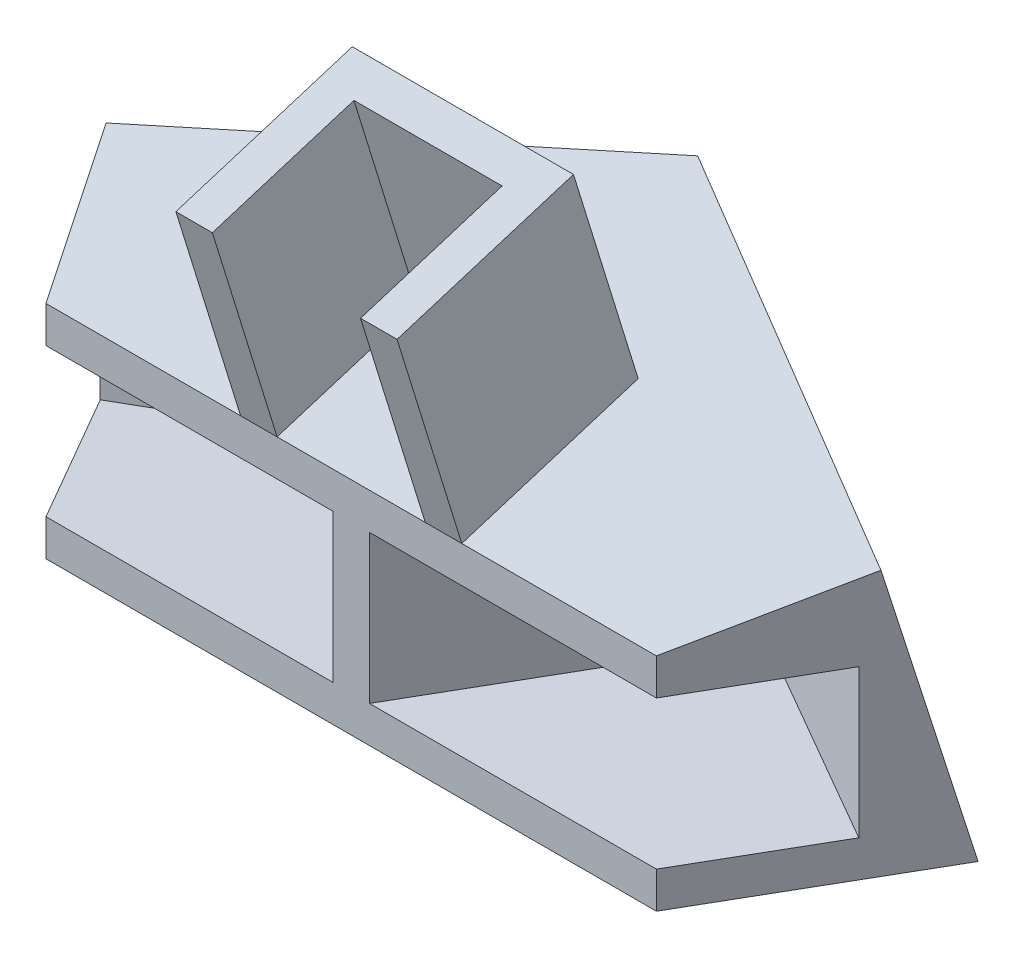
SolidWorks part; units mm, degrees
ref_plane "Front Plane" through (0, 0, 0) normal (0, 0, 1) x (1, 0, 0)
ref_plane "Top Plane" through (0, 0, 0) normal (0, 1, 0) x (1, 0, 0)
ref_plane "Right Plane" through (0, 0, 0) normal (1, 0, 0) x (0, 0, -1)
sketch "Sketch1" plane through (0, 0, 0) normal (0, 1, 0) x (1, 0, 0)
  line L0 (0, 0) -> (0, -24.1399) construction
  line L4 (0, 0) -> (-41.8115, -24.1399) construction
  line L5 (-41.8115, -24.1399) -> (0, -24.1399) construction
  line L6 (-41.8115, -24.1399) -> (-44.3115, -19.8098) construction
  line L7 (-44.3115, -19.8098) -> (0, 5.7735) construction
  line L8 (0, 5.7735) -> (0, 0) construction
  line L9 (-44.3115, -19.8098) -> (-51.9615, -6.5596) construction
  line L10 (0, 5.7735) -> (0, 23.4404) construction
  line L11 (-51.9615, -6.5596) -> (0, 23.4404) construction
  line L12 (-51.9615, -6.5596) -> (-54.4615, -2.2295) construction
  line L13 (-54.4615, -2.2295) -> (0, 29.2139) construction
  line L14 (0, 29.2139) -> (0, 23.4404) construction
  arc A0 (0, -3.7897) -> (-3.2819, -1.8948) centre (0, 0) cw construction
sketch "Sketch3" plane through (0, 0, 0) normal (0, 1, 0) x (1, 0, 0)
  line L0 (-54.4615, -2.2295) -> (-41.8115, -24.1399)
  line L1 (-41.8115, -24.1399) -> (0, -24.1399)
  line L2 (0, -24.1399) -> (0, 29.2139)
  line L3 (0, 29.2139) -> (-54.4615, -2.2295) construction
  line L4 (-54.4615, -2.2295) -> (-65.1668, 16.3126)
  line L5 (-65.1668, 16.3126) -> (0, 53.9367)
  line L6 (0, 53.9367) -> (0, 29.2139)
extrude "Boss-Extrude2" add sketch "Sketch3" along normal blind 5
sketch "Sketch4" plane through (0, 5, 0) normal (0, 1, 0) x (1, 0, 0)
  line L0 (-51.9615, -6.5596) -> (0, 23.4404)
  line L1 (-54.4615, -2.2295) -> (0, 29.2139) construction
  line L2 (-54.4615, -2.2295) -> (-51.9615, -6.5596)
  line L3 (0, 29.2139) -> (0, 23.4404)
  line L4 (-65.1668, 16.3126) -> (-54.4615, -2.2295)
  line L5 (-65.1668, 16.3126) -> (0, 53.9367)
  line L6 (0, 53.9367) -> (0, 29.2139)
extrude "Boss-Extrude3" add sketch "Sketch4" along normal blind 20.3
sketch "Sketch5" plane through (0, 25.3, 0) normal (0, 1, 0) x (1, 0, 0)
  line L0 (-65.1668, 16.3126) -> (-41.8115, -24.1399)
  line L1 (-41.8115, -24.1399) -> (0, -24.1399)
  line L2 (0, -24.1399) -> (0, 53.9367)
  line L3 (0, 53.9367) -> (-65.1668, 16.3126)
extrude "Boss-Extrude4" add sketch "Sketch5" along normal blind 5
sketch "Sketch7" plane through (0, 30.3, 0) normal (0, 1, 0) x (1, 0, 0)
  line L0 (-65.1668, 16.3126) -> (0, 53.9367)
  line L1 (0, 53.9367) -> (0, -24.1399)
  line L2 (0, -24.1399) -> (-41.8115, -24.1399)
  line L3 (-41.8115, -24.1399) -> (-65.1668, 16.3126)
extrude "Boss-Extrude5" add sketch "Sketch7" along normal blind 50
sketch "Sketch8" plane through (-41.8115, 0, 24.1399) normal (-0.866, 0, 0.5) x (0.5, 0, 0.866)
  line L0 (-32.2555, 0) -> (-18.9882, 49.5142) construction
  line L1 (-46.7105, 0) -> (0, 0) construction
  line L2 (-20.3, 25.3) -> (-25.1296, 26.5941) construction
  line L4 (-32.2555, 0) -> (-32.2555, 38.5962) construction
  line L5 (-20.3, 25.3) -> (-25.4764, 25.3) construction
  arc A0 (-32.2555, 20.5917) -> (-26.926, 19.89) centre (-32.2555, 0) cw construction
sketch "Sketch9" plane through (-41.8115, 0, 24.1399) normal (-0.866, 0, 0.5) x (0.5, 0, 0.866)
  line L0 (0, 25.3) -> (0, 30.3) construction
  line L1 (0, 80.3) -> (0, 25.3) construction
  line L2 (0, 30.3) -> (-24.1366, 30.3) construction
  line L3 (-32.2555, 0) -> (-18.9882, 49.5142) construction
  line L4 (-24.1366, 30.3) -> (-32.2555, 0) construction
  line L5 (-32.2555, 0) -> (-46.7105, 0) construction
  line L6 (-46.7105, 0) -> (-46.7105, 80.3) construction
  line L7 (-46.7105, 80.3) -> (0, 80.3) construction
  line L8 (0, 80.3) -> (0, 30.3) construction
sketch "Sketch11" plane through (-41.8115, 0, 24.1399) normal (-0.866, 0, 0.5) x (0.5, 0, 0.866)
  line L0 (-24.1366, 30.3) -> (-20.9029, 42.3683) construction
  line L1 (-24.1366, 30.3) -> (-32.2555, 0) construction
  line L2 (0, 30.3) -> (-22.5198, 36.3342) construction
sketch "Sketch12" plane through (-41.8115, 0, 24.1399) normal (-0.866, 0, 0.5) x (0.5, 0, 0.866)
  line L4 (-46.7105, 80.3) -> (-46.7105, 0)
  line L5 (-46.7105, 0) -> (-32.2555, 0)
  line L6 (-46.7105, 80.3) -> (-10.7392, 80.3)
  line L7 (-32.2555, 0) -> (-10.7392, 80.3)
  line L8 (-32.2555, 0) -> (-18.9882, 49.5142) construction
extrude "Cut-Extrude5" cut sketch "Sketch12" against normal through all
sketch "Sketch16" plane through (0, 0, 0) normal (1, 0, 0) x (0, 0, -1)
  line L0 (-24.1399, 25.3) -> (-24.1399, 30.3) construction
  line L1 (-24.1399, 80.3) -> (-24.1399, 25.3) construction
  line L2 (-24.1399, 30.3) -> (23.3267, 44.9862)
  line L3 (37.2454, 0) -> (12.4005, 80.3) construction
  line L4 (-24.1399, 30.3) -> (-24.1399, 80.3)
  line L5 (-24.1399, 80.3) -> (12.4005, 80.3)
  line L6 (12.4005, 80.3) -> (23.3267, 44.9862)
extrude "Cut-Extrude6" cut sketch "Sketch16" against normal through all
sketch "Sketch17" plane through (0, 34.4692, 10.6648) normal (0, 0.9553, 0.2956) x (1, 0, 0)
  line L0 (0, -14.1053) -> (-10.15, -14.1053) construction
  line L1 (-41.8115, -14.1053) -> (0, -14.1053) construction
  line L2 (-10.15, -14.1053) -> (-10.15, 6.1947)
  line L3 (-10.15, 6.1947) -> (0, 6.1947)
  line L4 (0, -14.1053) -> (0, 35.5813) construction
  line L5 (-10.15, -14.1053) -> (-15.15, -14.1053)
  line L6 (0, 6.1947) -> (0, 11.1947)
  line L7 (0, 11.1947) -> (-15.15, 11.1947)
  line L8 (-15.15, 11.1947) -> (-15.15, -14.1053)
extrude "Boss-Extrude6" add sketch "Sketch17" along normal blind 30
sketch "Sketch18" plane through (0, 5, 0) normal (0, 1, 0) x (1, 0, 0)
  line L0 (0, -24.1399) -> (-2.5, -24.1399)
  line L1 (-41.8115, -24.1399) -> (0, -24.1399) construction
  line L2 (-2.5, -24.1399) -> (-22.4779, 10.4628)
  line L3 (-51.9615, -6.5596) -> (0, 23.4404) construction
  line L4 (-22.4779, 10.4628) -> (0, 23.4404)
  line L5 (0, 23.4404) -> (0, -24.1399)
extrude "Boss-Extrude7" add sketch "Sketch18" along normal up to surface (20.3 mm away) up to face at (-23.4433, 25.3, 7.8497)
mirror "Mirror2" about plane through (0, 5, -53.9367) normal (-1, 0, 0) of "Boss-Extrude7", "Boss-Extrude6", "Cut-Extrude6", "Cut-Extrude5", "Boss-Extrude5", "Boss-Extrude4", "Boss-Extrude3", "Boss-Extrude2"
